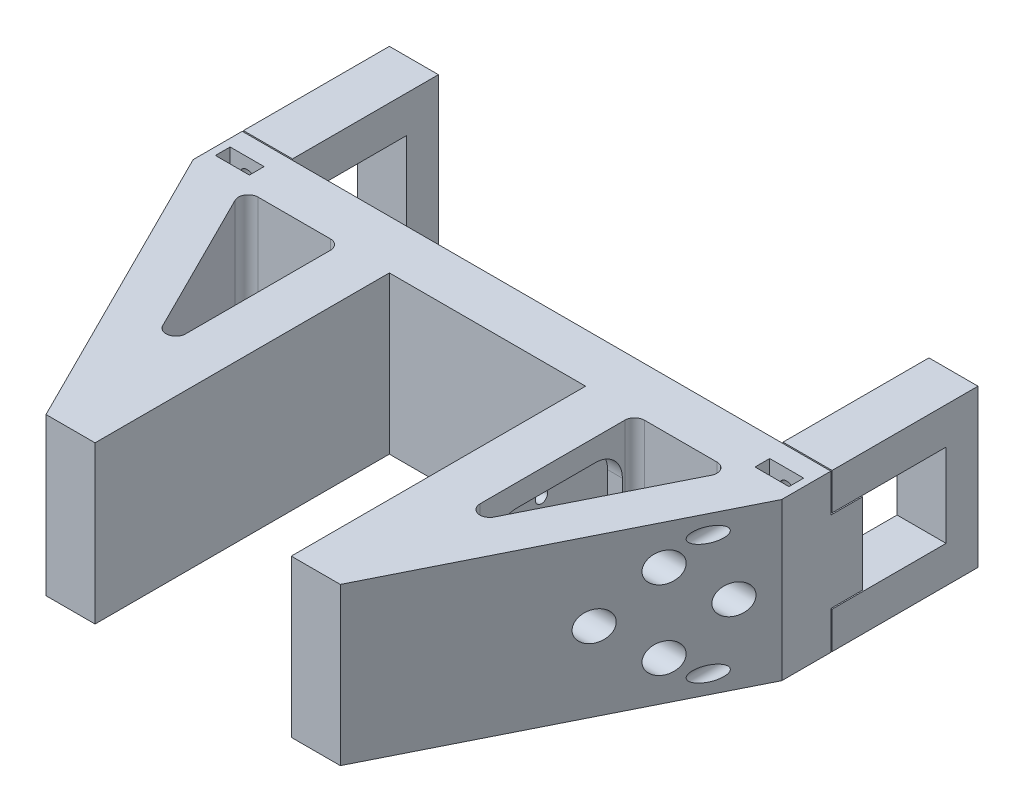
SolidWorks part; units mm, degrees
ref_plane "Front Plane" through (0, 0, 0) normal (0, 0, 1) x (1, 0, 0)
ref_plane "Top Plane" through (0, 0, 0) normal (0, 1, 0) x (1, 0, 0)
ref_plane "Right Plane" through (0, 0, 0) normal (1, 0, 0) x (0, 0, -1)
ref_axis "X" through (-88.99, 0, 0) along (1, 0, 0)
ref_axis "Y" through (0, 55, 0) along (0, -1, 0)
ref_axis "Z" through (0, 0, -88.99) along (0, 0, 1)
sketch "Sketch1" plane through (0, 0, 0) normal (0, 1, 0) x (1, 0, 0)
  line L0 (-50, 0) -> (50, 0)
  line L1 (50, 0) -> (50, 30)
  line L2 (50, 30) -> (60, 30)
  line L3 (60, 30) -> (60, -10)
  line L4 (60, -10) -> (30, -10)
  line L5 (30, -10) -> (30, -70)
  line L6 (30, -70) -> (20, -70)
  line L7 (20, -70) -> (20, -10)
  line L8 (20, -10) -> (-20, -10)
  line L9 (0, 0) -> (0, -10) construction
  line L10 (60, -10) -> (30, -70)
  line L11 (30, -50) -> (50, -10)
  line L12 (-30, -50) -> (-50, -10)
  line L13 (-60, -10) -> (-30, -70)
  line L14 (-20, -70) -> (-20, -10)
  line L15 (-30, -70) -> (-20, -70)
  line L16 (-30, -10) -> (-30, -70)
  line L17 (-60, -10) -> (-30, -10)
  line L18 (-60, 30) -> (-60, -10)
  line L19 (-50, 30) -> (-60, 30)
  line L20 (-50, 0) -> (-50, 30)
  dimension "D1" = 50
  dimension "D2" = 60
  dimension "D3" = 10
  dimension "D4" = 10
  dimension "D5" = 10
  dimension "D6" = 30
  dimension "D7" = 120
  dimension "D8" = 100
  dimension "D9" = 40
extrude "Main Extrude" add sketch "Sketch1" along normal mid plane 32 contours L0 L9 L8 L7 L6 L5 L4 L3 L2 L1 | L9 L0 L20 L19 L18 L17 L16 L15 L14 L8 | L11 L5 L10 L4 | L17 L13 L16 L12 region at (-25, 0, 1.1662) region at (25, 0, 1.1662) region at (-42.6667, 0, 35.3333) region at (42.6667, 0, 35.3333)
sketch "Sketch2" plane through (0, 0, 0) normal (1, 0, 0) x (0, 0, -1)
  line L0 (0, 0) -> (15, 0) construction
  line L1 (6.5, 8.5) -> (23.5, 8.5)
  line L2 (6.5, 8.5) -> (6.5, -8.5)
  line L3 (6.5, -8.5) -> (23.5, -8.5)
  line L4 (23.5, 8.5) -> (23.5, -8.5)
  line L5 (6.5, 8.5) -> (23.5, -8.5) construction
  line L6 (6.5, -8.5) -> (23.5, 8.5) construction
  point P0 (15, 0)
  dimension "D1" = 17
  dimension "D2" = 15
extrude "Drive Motor Cutout" cut sketch "Sketch2" against normal through all both and the other way through all
fillet "Sharp Edge Removal" radius 2 6 edges at (30, 0, 50) (50, 0, 10) (30, 0, 10) (-30, 0, 50) (-50, 0, 10) (-30, 0, 10)
sketch3d "Component Placement"
  line L0 (0, 0, 0) -> (0, 0, 10) construction
  line L1 (0, 0, 10) -> (0, 0, 26) construction
  line L2 (0, 0, 26) -> (20, 0, 26) construction
  point P5 (0, 0, 0)
  dimension "D1" = 16
sketch "Weapon Motor Mount Holes" plane through (30, 0, 0) normal (1, 0, 0) x (0, 0, -1)
  line L0 (-34, -11.5) -> (-18, -11.5)
  line L1 (-12.5, -6) -> (-12.5, 6)
  line L2 (-18, 11.5) -> (-34, 11.5)
  line L3 (-39.5, 6) -> (-39.5, -6)
  line L4 (-39, 6) -> (-39, -6)
  line L5 (-34, -11) -> (-18, -11)
  line L6 (-13, -6) -> (-13, 6)
  line L7 (-18, 11) -> (-34, 11)
  line L8 (-39, 6) -> (-39, -6) construction
  line L9 (-34, -11) -> (-18, -11) construction
  line L10 (-13, -6) -> (-13, 6) construction
  line L11 (-18, 11) -> (-34, 11) construction
  circle A0 centre (-16.5, 0) radius 1.25 construction
  circle A1 centre (-35.5, 0) radius 1.25 construction
  circle A2 centre (-26, 8) radius 1.25 construction
  circle A3 centre (-26, -8) radius 1.25 construction
  circle A4 centre (-16.5, 0) radius 1.25
  circle A5 centre (-35.5, 0) radius 1.25
  circle A6 centre (-26, 8) radius 1.25
  circle A7 centre (-26, -8) radius 1.25
  circle A8 centre (-26, 8) radius 3
  circle A9 centre (-16.5, 0) radius 3
  circle A10 centre (-26, -8) radius 3
  circle A11 centre (-35.5, 0) radius 3
  arc A12 (-39.5, -6) -> (-34, -11.5) centre (-34, -6) ccw
  arc A13 (-18, -11.5) -> (-12.5, -6) centre (-18, -6) ccw
  arc A14 (-12.5, 6) -> (-18, 11.5) centre (-18, 6) ccw
  arc A15 (-34, 11.5) -> (-39.5, 6) centre (-34, 6) ccw
  arc A16 (-39, -6) -> (-34, -11) centre (-34, -6) ccw
  arc A17 (-18, -11) -> (-13, -6) centre (-18, -6) ccw
  arc A18 (-13, 6) -> (-18, 11) centre (-18, 6) ccw
  arc A19 (-34, 11) -> (-39, 6) centre (-34, 6) ccw
  arc A20 (-39, -6) -> (-34, -11) centre (-34, -6) ccw construction
  arc A21 (-18, -11) -> (-13, -6) centre (-18, -6) ccw construction
  arc A22 (-13, 6) -> (-18, 11) centre (-18, 6) ccw construction
  arc A23 (-34, 11) -> (-39, 6) centre (-34, 6) ccw construction
  dimension "D1" = 6
  dimension "D2" = 0
  dimension "D3" = 0.5
extrude "Cut-Extrude1" cut sketch "Weapon Motor Mount Holes" against normal up to surface (10 mm away) contours A5 | A6 | A4 | A7 region at (30, 0, 16.5) region at (30, 0, 35.5) region at (30, 8, 26) region at (30, -8, 26) up to face at (20, 0, 40)
extrude "Cut-Extrude2" cut sketch "Weapon Motor Mount Holes<3>" along normal through all contours A9 | A8 | A11 | A10
sketch "Weapon Motor Mount Holes<3>" plane through (30, 0, 0) normal (1, 0, 0) x (0, 0, -1) same geometry as "Weapon Motor Mount Holes"
extrude "Cut-Extrude3" cut sketch "Weapon Motor Mount Holes<4>" against normal blind 3 contours A15 L3 A12 L0 A13 L1 A14 L2
sketch "Weapon Motor Mount Holes<4>" plane through (30, 0, 0) normal (1, 0, 0) x (0, 0, -1) same geometry as "Weapon Motor Mount Holes"
sketch "Sketch4" plane through (0, 0, 0) normal (1, 0, 0) x (0, 0, -1)
  line L0 (0, 16) -> (0, -16) construction
  line L1 (0, 16) -> (0, -16)
  line L2 (6.5, -8.5) -> (6.5, 8.5) construction
  line L3 (6.5, -8.5) -> (6.5, 8.5)
  line L4 (6.5, 8.5) -> (0, 8.5)
  line L5 (6.5, -8.5) -> (0, -8.5)
  line L6 (6.5, -8.5) -> (6.5, -8.25)
  line L7 (6.5, -8.25) -> (0.25, -8.25)
  line L8 (6.5, 8.5) -> (6.5, 8.25)
  line L9 (6.5, 8.25) -> (0.25, 8.25)
  line L10 (0, 16) -> (0.25, 16)
  line L11 (0.25, 16) -> (0.25, 8.25)
  line L12 (0, -16) -> (0.25, -16)
  line L13 (0.25, -16) -> (0.25, -8.25)
  line L14 (0.25, 8.25) -> (0, 8.25)
  line L16 (0.25, -8.25) -> (0, -8.25)
  dimension "D1" = 0.25
extrude "Cut-Extrude4" cut sketch "Sketch4" against normal through all both and the other way through all contours L11 L10 L1 L4 L8 L9 | L14 L11 L4 L1 | L4 L11 L9 L3 | L12 L13 L5 L1 | L13 L16 L1 L5 | L13 L5 L3 L7 region at (0, 12.25, -0.125) region at (0, 8.375, -0.125) region at (0, 8.375, -3.375) region at (0, -8.375, -0.125) region at (0, -12.25, -0.125) region at (0, -8.375, -3.375)
sketch "Sketch5" plane through (0, 0, -0.25) normal (0, 0, 1) x (1, 0, 0)
  line L0 (55, 16) -> (55, 8.5) construction
  line L1 (55, -8.5) -> (55, -16) construction
  line L4 (50, 8.5) -> (60, 8.5)
  line L5 (60, 8.5) -> (60, 16)
  line L6 (60, 16) -> (50, 16)
  line L7 (50, 16) -> (50, 8.5)
  line L8 (50, 8.5) -> (60, 8.5)
  line L9 (60, 8.5) -> (60, 16)
  line L10 (60, 16) -> (50, 16)
  line L11 (50, 16) -> (50, 8.5)
  line L12 (50, -8.5) -> (50, -16)
  line L13 (50, -16) -> (60, -16)
  line L14 (60, -16) -> (60, -8.5)
  line L15 (60, -8.5) -> (50, -8.5)
  line L16 (50, -8.5) -> (50, -16)
  line L17 (50, -16) -> (60, -16)
  line L18 (60, -16) -> (60, -8.5)
  line L19 (60, -8.5) -> (50, -8.5)
  circle A0 centre (55, 12.25) radius 1.5
  circle A1 centre (55, -12.25) radius 1.5
  circle A2 centre (55, 12.25) radius 3
  circle A3 centre (55, -12.25) radius 3
  point P12 (55, -11.75)
  dimension "D3" = 3
  dimension "D4" = 6
  dimension "D1" = 0
  dimension "D2" = 0
extrude "Cut-Extrude5" cut sketch "Sketch5" against normal through all and the other way through all contours A0 | A1 region at (55, 12.25, -0.25) region at (55, -12.25, -0.25)
extrude "Cut-Extrude6" cut sketch "Sketch5<3>" along normal blind 4 from surface contours A2 | A3 starting at face at (56.5, 12.25, -30)
sketch "Sketch5<3>" plane through (0, 0, -0.25) normal (0, 0, 1) x (1, 0, 0) same geometry as "Sketch5"
ref_plane "Plane1" through (0, 0, 4) normal (0, 0, -1) x (-1, 0, 0)
sketch "Sketch6" plane through (0, 0, 4) normal (0, 0, -1) x (-1, 0, 0)
  line L0 (60, 16) -> (-60, 16) construction
  line L1 (-58.4641, 12.25) -> (-56.7321, 9.25)
  line L2 (-56.7321, 9.25) -> (-53.2679, 9.25)
  line L3 (-53.2679, 9.25) -> (-51.5359, 12.25)
  line L4 (-51.5359, 12.25) -> (-53.2679, 15.25) construction
  line L5 (-53.2679, 15.25) -> (-56.7321, 15.25) construction
  line L6 (-56.7321, 15.25) -> (-58.4641, 12.25) construction
  line L7 (-53.2679, -15.25) -> (-51.5359, -12.25) construction
  line L8 (-51.5359, -12.25) -> (-53.2679, -9.25)
  line L9 (-53.2679, -9.25) -> (-56.7321, -9.25)
  line L10 (-56.7321, -9.25) -> (-58.4641, -12.25)
  line L11 (-58.4641, -12.25) -> (-56.7321, -15.25) construction
  line L12 (-56.7321, -15.25) -> (-53.2679, -15.25) construction
  line L13 (60, 16) -> (-60, 16)
  line L14 (60, -16) -> (-60, -16) construction
  line L15 (60, -16) -> (-60, -16)
  line L16 (-58.4641, 12.25) -> (-58.4641, 16)
  line L17 (-51.5359, 12.25) -> (-51.5359, 16)
  line L18 (-58.4641, -12.25) -> (-58.4641, -16)
  line L19 (-51.5359, -12.25) -> (-51.5359, -16)
  circle A0 centre (-55, -12.25) radius 1.5 construction
  circle A1 centre (-55, 12.25) radius 1.5 construction
  circle A2 centre (-55, -12.25) radius 1.5 construction
  circle A3 centre (-55, 12.25) radius 1.5 construction
  circle A4 centre (-55, 12.25) radius 3 construction
  circle A5 centre (-55, -12.25) radius 3 construction
  dimension "D1" = 6
extrude "Cut-Extrude7" cut sketch "Sketch6" against normal blind 3 contours L3 L17 L13 L16 L1 L2 | L19 L8 L9 L10 L18 L15 region at (55, 12.9219, 4) region at (55, -12.9219, 4)
mirror "Mirror1" about plane through (0, 0, 0) normal (1, 0, 0) of "Cut-Extrude7", "Cut-Extrude6", "Cut-Extrude5"
